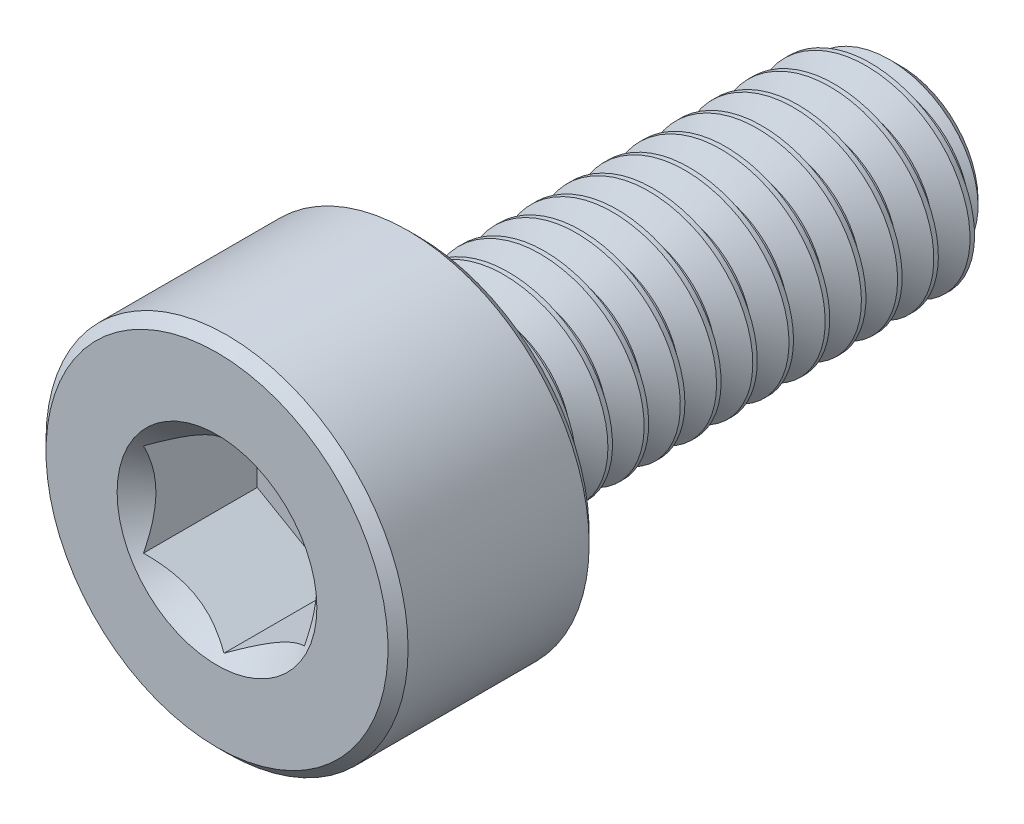
SolidWorks part; units mm, degrees
ref_plane "Front Plane" through (0, 0, 0) normal (0, 0, 1) x (1, 0, 0)
ref_plane "Top Plane" through (0, 0, 0) normal (0, 1, 0) x (1, 0, 0)
ref_plane "Right Plane" through (0, 0, 0) normal (1, 0, 0) x (0, 0, -1)
sketch "Sketch1" plane through (0, 0, 0) normal (1, 0, 0) x (0, 0, -1)
  line L0 (-4.25, 0) -> (4.25, 0) construction
  line L1 (4.25, 0) -> (4.25, 0.9577) construction
  line L2 (4.25, 0.9577) -> (3.9577, 1.25) construction
  line L3 (3.9577, 1.25) -> (3.9125, 1.25) construction
  line L4 (3.9125, 1.25) -> (-1.75, 1.25) construction
  line L5 (-1.75, 1.25) -> (-1.75, 2.25) construction
  line L6 (-1.75, 2.25) -> (-4.25, 2.25) construction
  line L7 (-4.25, 2.25) -> (-4.25, 0) construction
  line L8 (4.25, 0.9577) -> (4.25, 1.25) construction
  line L9 (4.2219, 1.2987) -> (4.4469, 0.909) construction
  line L10 (4.4469, 0.909) -> (4.6719, 1.2987) construction
  line L11 (4.6719, 1.2987) -> (4.2219, 1.2987) construction
  line L12 (4.4469, 1.2987) -> (4.4469, 1.25) construction
  line L13 (4.4469, 0.909) -> (4.4469, 0.9577) construction
  line L14 (4.4187, 0.9577) -> (4.475, 0.9577) construction
  line L15 (4.25, 1.25) -> (4.6437, 1.25) construction
  line L16 (4.2359, 1.2744) -> (4.6578, 1.2744) construction
  line L17 (4.25, 0) -> (4.25, -1.25) construction
  line L18 (-1.875, 2.25) -> (-1.75, 2.125) construction
  line L19 (-4.125, 2.25) -> (-4.25, 2.125) construction
  line L20 (-1.75, 1.25) -> (-1.75, 0) construction
  line L21 (-1.75, 0.625) -> (0.25, 0.625) construction
  line L22 (0.25, 0.625) -> (2.25, 0.625) construction
  line L23 (2.25, 0.625) -> (4.25, 0.625) construction
  line L24 (0.25, 0.625) -> (0.25, 1.25) construction
  line L25 (0.25, 1.25) -> (0.25, 2.25) construction
  line L26 (2.25, 0.625) -> (2.25, 2.25) construction
  point P0 (-4.25, 1)
  point P3 (3.125, 1.25)
  point P4 (0, 0)
  point P18 (2.25, 1.25)
  point P22 (4.4469, 0.9577)
  point P24 (3.9125, 1.25)
  point P25 (4.4469, 1.25)
  point P28 (4.4469, 1.2744)
  point P29 (3.125, -1.25)
  point P30 (0.25, 1.25)
  point P31 (-3, 2.25)
  point P37 (-2.1875, 2.25)
  point P38 (-4.0625, 2.25)
  point P45 (0.25, 0.625)
  point P46 (2.25, 0.625)
  dimension "D2" = 0.0563
  dimension "D7" = 0.125
  dimension "D8" = 0.125
  dimension "D9" = 0.125
  dimension "D10" = 0.0625
  dimension "D11" = 0.3125
  dimension "Drive Size" = 2
  dimension "Head Diameter" = 4.5
  dimension "Head Height" = 2.5
  dimension "Thread Pitch" = 0.45
  dimension "Thread Dia" = 2.5
  dimension "Length" = 6
  dimension "D12" = 0.3375
  dimension "D4" = 1.125
  dimension "D3" = 45
sketch "Sketch2" plane through (0, 0, 0) normal (1, 0, 0) x (0, 0, -1)
  line L0 (-4.25, 0) -> (-4.25, 2.125)
  line L1 (-4.125, 2.25) -> (-1.875, 2.25)
  line L2 (-1.75, 2.125) -> (-1.75, 1.375)
  line L4 (3.9577, 1.25) -> (4.25, 0.9577)
  line L5 (4.25, 0.9577) -> (4.25, 0)
  line L6 (-1.75, 2.25) -> (-4.25, 2.25) construction
  line L7 (4.25, 0) -> (-4.25, 0)
  line L8 (-4.125, 2.25) -> (-4.25, 2.125) construction
  line L10 (-4.125, 2.25) -> (-4.25, 2.125)
  line L14 (-1.875, 2.25) -> (-1.75, 2.125) construction
  line L16 (-1.875, 2.25) -> (-1.75, 2.125)
  line L17 (-1.75, 1.25) -> (-1.75, 2.25) construction
  line L19 (-1.625, 1.25) -> (3.9577, 1.25)
  line L20 (3.9125, 1.25) -> (-1.75, 1.25) construction
  arc A1 (-1.75, 1.375) -> (-1.625, 1.25) centre (-1.625, 1.375) ccw
  dimension "D3" = 0.125
revolve "Revolve1" add sketch "Sketch2" angle 360 about L7
sketch "Sketch3" plane through (0, 0, 4.25) normal (0, 0, 1) x (1, 0, 0)
  line L1 (1, -0.5774) -> (1, 0.5774)
  line L2 (1, 0.5774) -> (0, 1.1547)
  line L3 (0, 1.1547) -> (-1, 0.5774)
  line L4 (-1, 0.5774) -> (-1, -0.5774)
  line L5 (-1, -0.5774) -> (0, -1.1547)
  line L6 (0, -1.1547) -> (1, -0.5774)
  circle A0 centre (0, 0) radius 1 construction
  circle A1 centre (0, 0) radius 2.25 construction
  circle A2 centre (0, 0) radius 2.25 construction
  circle A3 centre (0, 0) radius 1.1547 construction
  point P13 (0, 0)
  dimension "D1" = 2.3094
extrude "Cut-Extrude1" cut sketch "Sketch3" against normal offset from surface (1.5 mm away) 1 up to face at (0, 2.125, 1.75)
sketch "Sketch4" plane through (0, 0, 4.25) normal (0, 0, 1) x (1, 0, 0)
  circle A0 centre (0, 0) radius 1.2413
  dimension "D1" = 2.4826
extrude "Cut-Extrude2" cut sketch "Sketch4" against normal up to vertex (1.25 mm away) draft 45 up to point (0, 2.25, 3)
sketch "Sketch11" plane through (0, 0, 0) normal (1, 0, 0) x (0, 0, -1)
  line L0 (-4.25, 0) -> (4.25, 0) construction
  line L1 (-4.25, 0) -> (4.25, 0) construction
  line L2 (-0.625, 0) -> (-0.625, 1.25) construction
  line L3 (3.9125, 1.25) -> (-1.75, 1.25) construction
  line L4 (3.125, 0) -> (3.125, 1.25) construction
  line L6 (4.25, 0.9577) -> (4.25, 1.25) construction
  point P2 (-0.625, 0)
  point P3 (3.125, 0)
  dimension "D1" = 1.125
  dimension "D2" = 1.125
sketch "Sketch6" plane through (0, 0, -4.25) normal (0, 0, -1) x (-1, 0, 0)
  circle A0 centre (0, 0) radius 1.25
curve "Helix/Spiral1" pitch 0.45 height 6.45 radius 1.25 centre (0, 0, -4.25) axis (0, 0, 1) start towards (0, 1, 0)
sketch "Sketch10" plane through (0, 0, 0) normal (1, 0, 0) x (0, 0, -1)
  line L0 (-1.625, -2.25) -> (-1.625, 2.25)
  line L5 (-4.25, 0) -> (4.25, 0) construction
  line L6 (-1.625, 1.25) -> (-1.625, -1.25) construction
  point P3 (-1.625, 0)
split "Split1" trim tools "Sketch10" bodies to split 106 resulting bodies 114 115
sketch "Sketch7" plane through (0, 0, 0) normal (1, 0, 0) x (0, 0, -1)
  line L0 (4.2359, 1.2744) -> (4.6578, 1.2744)
  line L1 (4.6578, 1.2744) -> (4.475, 0.9577)
  line L2 (4.475, 0.9577) -> (4.4187, 0.9577)
  line L3 (4.4187, 0.9577) -> (4.2359, 1.2744)
sweep "Cut-Sweep1" cut profiles "Sketch7" path "Helix/Spiral1" align with end faces yes
sketch "Sketch8" plane through (0, 0, 0) normal (1, 0, 0) x (0, 0, -1)
  line L0 (-1.75, 0) -> (-1.75, 1.25)
  line L1 (-1.625, -1.25) -> (-1.625, 1.25) construction
  line L2 (-1.75, 1.25) -> (-1.625, 1.25)
  line L4 (-1.625, 1.25) -> (-0.9033, 0)
  line L5 (-0.9033, 0) -> (-1.75, 0)
  line L6 (3.9125, 1.25) -> (-1.75, 1.25) construction
  line L7 (-4.25, 0) -> (4.25, 0) construction
  dimension "D1" = 60
revolve "Revolve2" add sketch "Sketch8" angle 360 about L5
equation "\"D2@Sketch1\" = \"Thread Pitch@Sketch1\" / 8"
equation "\"D4@Helix/Spiral1\" = \"Thread Pitch@Sketch1\""
equation "\"D7@Sketch1\" = \"Head Height@Sketch1\" * .05"
equation "\"D8@Sketch1\"=\"D7@Sketch1\""
equation "\"D9@Sketch1\"=\"D7@Sketch1\""
equation "\"D10@Sketch1\"=\"D7@Sketch1\"/2"
equation "\"D11@Sketch1\"=\"D10@Sketch1\"*5"
equation "\"D4@Sketch1\"=\"Thread Pitch@Sketch1\"*2.5"
equation "\"D12@Sketch1\"=\"Thread Pitch@Sketch1\"*.75"
equation "\"D3@Helix/Spiral1\"=\"Length@Sketch1\"+\"Thread Pitch@Sketch1\""
equation "\"D3@Sketch2\"=\"Thread Dia@Sketch1\"*0.05"
equation "\"D1@Sketch11\"=\"Length@Sketch1\"*0.1875"
equation "\"D2@Sketch11\"=\"D1@Sketch11\""
equation "\"D1@Sketch4\"=\"D1@Sketch3\"*1.075"
